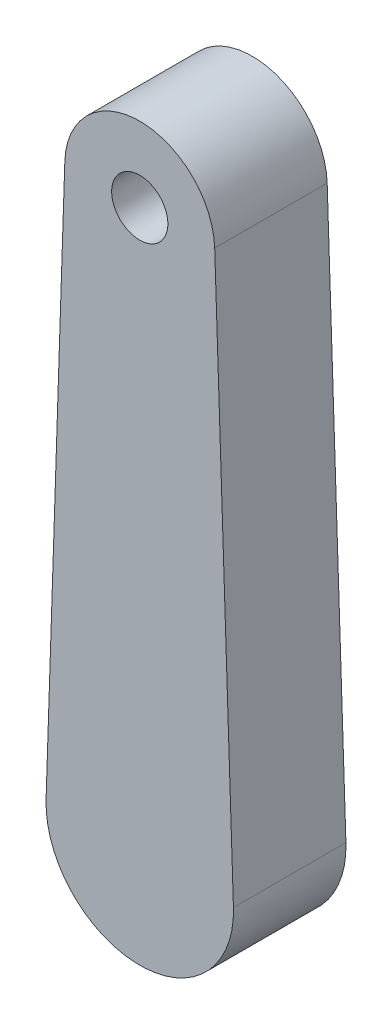
SolidWorks part; units mm, degrees
ref_plane "Front Plane" through (0, 0, 0) normal (0, 0, 1) x (1, 0, 0)
ref_plane "Top Plane" through (0, 0, 0) normal (0, 1, 0) x (1, 0, 0)
ref_plane "Right Plane" through (0, 0, 0) normal (1, 0, 0) x (0, 0, -1)
sketch "Sketch1" plane through (0, 0, 0) normal (0, 0, 1) x (1, 0, 0)
  line L0 (-1.9912, 16.1875) -> (-3.4846, 0.3281)
  line L1 (3.4846, 0.3281) -> (1.9912, 16.1875)
  arc A0 (-3.4846, 0.3281) -> (3.4846, 0.3281) centre (0, 0) ccw
  arc A1 (1.9912, 16.1875) -> (-1.9912, 16.1875) centre (0, 16) ccw
  dimension "D1" = 7
  dimension "D3" = 4
  dimension "D2" = 16
sketch "Sketch2" plane through (0, 0, 0) normal (0, 0, 1) x (1, 0, 0)
  line L0 (0, 0) -> (0, 30) construction
  line L4 (-4.9972, 0.1667) -> (-3.9978, 30.1333)
  line L5 (4.9972, 0.1667) -> (3.9978, 30.1333)
  line L6 (0, 0) -> (0, 30) construction
  arc A3 (3.9978, 30.1333) -> (-3.9978, 30.1333) centre (0, 30) ccw
  arc A4 (-4.9972, 0.1667) -> (4.9972, 0.1667) centre (0, 0) ccw
  circle A5 centre (0, 30) radius 1.5
  dimension "D1" = 3
  dimension "D2" = 4
  dimension "D3" = 5
extrude "Boss-Extrude1" add sketch "Sketch2" along normal mid plane 6
extrude "Cut-Extrude1" cut sketch "Sketch1" against normal through all and the other way blind 1
ref_axis "Axis1" through (0, 30, 3) along (0, 0, -1)
ref_axis "Axis2" through (0, 0, 1) along (0, 0, -1)
